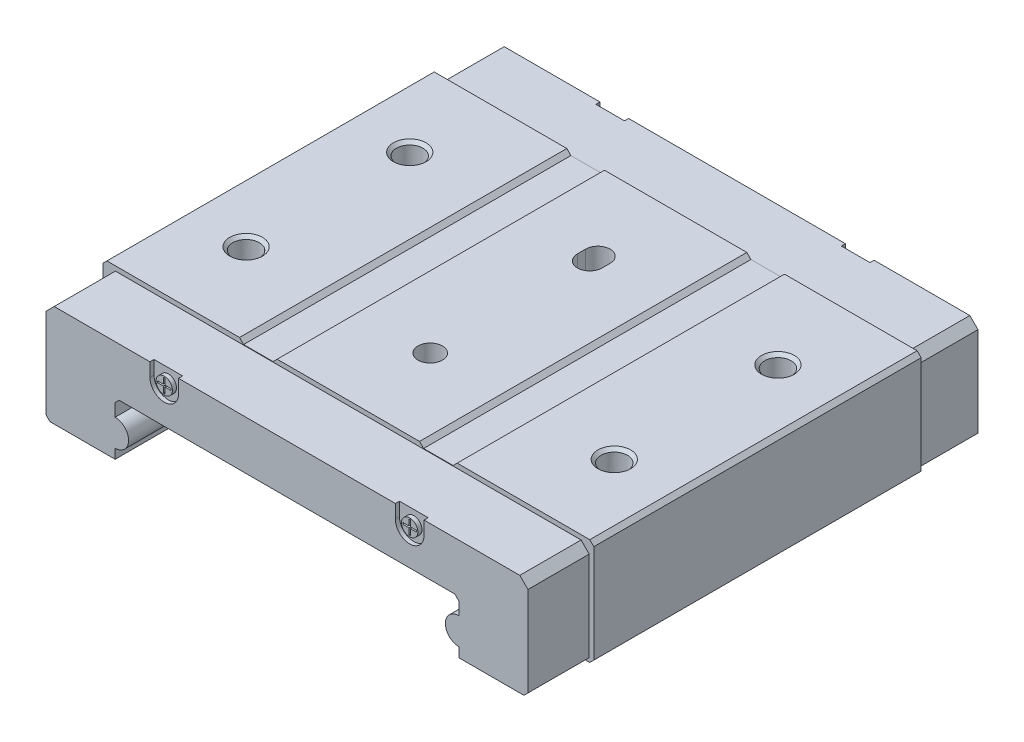
SolidWorks part; units mm, degrees
ref_plane "Front Plane" through (0, 0, 0) normal (0, 0, 1) x (1, 0, 0)
ref_plane "Top Plane" through (0, 0, 0) normal (0, 1, 0) x (1, 0, 0)
ref_plane "Right Plane" through (0, 0, 0) normal (1, 0, 0) x (0, 0, -1)
ref_plane "Plane1" through (0, 0, 0) normal (0, 0, 1) x (1, 0, 0)
sketch "Sketch1" plane through (0, 0, 0) normal (0, 0, 1) x (1, 0, 0)
  line L0 (-30, 12.505) -> (-30, 0.495)
  line L1 (-30, 0.495) -> (-29.505, 0)
  line L2 (-29.505, 0) -> (-21, 0)
  line L3 (-21, 0) -> (-21, 1.176)
  line L4 (-21, 4.456) -> (-21, 6.005)
  line L5 (-21, 6.005) -> (-20.505, 6.5)
  line L6 (-20.505, 6.5) -> (20.505, 6.5)
  line L7 (20.505, 6.5) -> (21, 6.005)
  line L8 (21, 6.005) -> (21, 4.456)
  line L9 (21, 1.176) -> (21, 0)
  line L10 (21, 0) -> (29.505, 0)
  line L11 (29.505, 0) -> (30, 0.495)
  line L12 (30, 0.495) -> (30, 12.505)
  line L13 (30, 12.505) -> (29.505, 13)
  line L14 (29.505, 13) -> (13.3, 13)
  line L15 (13.3, 13) -> (12.8, 12.5)
  line L16 (12.8, 12.5) -> (9.2, 12.5)
  line L17 (9.2, 12.5) -> (8.7, 13)
  line L18 (8.7, 13) -> (-8.7, 13)
  line L19 (-8.7, 13) -> (-9.2, 12.5)
  line L20 (-9.2, 12.5) -> (-12.8, 12.5)
  line L21 (-12.8, 12.5) -> (-13.3, 13)
  line L22 (-13.3, 13) -> (-29.505, 13)
  line L23 (-29.505, 13) -> (-30, 12.505)
  arc A0 (-21, 1.176) -> (-21, 4.456) centre (-21, 2.816) ccw
  arc A1 (21, 4.456) -> (21, 1.176) centre (21, 2.816) ccw
extrude "Boss-Extrude1" add sketch "Sketch1" against normal blind 20 and the other way blind 20
ref_plane "Plane2" through (0, 0, 20) normal (0, 0, 1) x (1, 0, 0)
sketch "Sketch2" plane through (0, 0, 20) normal (0, 0, 1) x (1, 0, 0)
  line L0 (-29.45, 11.453) -> (-29.45, 0.495)
  line L1 (-29.45, 0.495) -> (-28.955, 0)
  line L2 (-28.955, 0) -> (-21, 0)
  line L3 (-21, 0) -> (-21, 1.176)
  line L4 (-21, 4.456) -> (-21, 6.005)
  line L5 (-21, 6.005) -> (-20.505, 6.5)
  line L6 (-20.505, 6.5) -> (20.505, 6.5)
  line L7 (20.505, 6.5) -> (21, 6.005)
  line L8 (21, 6.005) -> (21, 4.456)
  line L9 (21, 1.176) -> (21, 0)
  line L10 (21, 0) -> (28.955, 0)
  line L11 (28.955, 0) -> (29.45, 0.495)
  line L12 (29.45, 0.495) -> (29.45, 11.453)
  line L13 (29.45, 11.453) -> (28.453, 12.45)
  line L14 (28.453, 12.45) -> (-28.453, 12.45)
  line L15 (-28.453, 12.45) -> (-29.45, 11.453)
  arc A0 (-21, 1.176) -> (-21, 4.456) centre (-21, 2.816) ccw
  arc A1 (21, 4.456) -> (21, 1.176) centre (21, 2.816) ccw
extrude "Boss-Extrude2" add sketch "Sketch2" against normal blind 7.5 and the other way blind 7.5
ref_plane "Plane3" through (0, 0, 20) normal (0, 0, 1) x (1, 0, 0)
sketch "Sketch3" plane through (0, 0, 20) normal (0, 0, 1) x (1, 0, 0)
  line L0 (-40, 40) -> (-40, -40)
  line L1 (-40, -40) -> (40, -40)
  line L2 (40, -40) -> (40, 40)
  line L3 (40, 40) -> (-40, 40)
  line L4 (-29.44, 11.443) -> (-29.44, 0.505)
  line L5 (-29.44, 0.505) -> (-28.945, 0.01)
  line L6 (-28.945, 0.01) -> (-21.01, 0.01)
  line L7 (-21.01, 0.01) -> (-21.01, 1.206)
  line L8 (-21.01, 4.446) -> (-21.01, 6.51)
  line L9 (-21.01, 6.51) -> (21.01, 6.51)
  line L10 (21.01, 6.51) -> (21.01, 4.446)
  line L11 (21.01, 1.206) -> (21.01, 0.01)
  line L12 (21.01, 0.01) -> (28.945, 0.01)
  line L13 (28.945, 0.01) -> (29.44, 0.505)
  line L14 (29.44, 0.505) -> (29.44, 11.443)
  line L15 (29.44, 11.443) -> (28.443, 12.44)
  line L16 (28.443, 12.44) -> (-28.443, 12.44)
  line L17 (-28.443, 12.44) -> (-29.44, 11.443)
  arc A0 (-21.01, 1.206) -> (-21.01, 4.446) centre (-21.01, 2.826) ccw
  arc A1 (21.01, 4.446) -> (21.01, 1.206) centre (21.01, 2.826) ccw
extrude "Cut-Extrude1" cut sketch "Sketch3" along normal blind 0.02
ref_plane "Plane4" through (0, 0, -20) normal (0, 0, 1) x (1, 0, 0)
sketch "Sketch4" plane through (0, 0, -20) normal (0, 0, 1) x (1, 0, 0)
  line L0 (-29.45, 11.453) -> (-29.45, 0.495)
  line L1 (-29.45, 0.495) -> (-28.955, 0)
  line L2 (-28.955, 0) -> (-21, 0)
  line L3 (-21, 0) -> (-21, 1.176)
  line L4 (-21, 4.456) -> (-21, 6.005)
  line L5 (-21, 6.005) -> (-20.505, 6.5)
  line L6 (-20.505, 6.5) -> (20.505, 6.5)
  line L7 (20.505, 6.5) -> (21, 6.005)
  line L8 (21, 6.005) -> (21, 4.456)
  line L9 (21, 1.176) -> (21, 0)
  line L10 (21, 0) -> (28.955, 0)
  line L11 (28.955, 0) -> (29.45, 0.495)
  line L12 (29.45, 0.495) -> (29.45, 11.453)
  line L13 (29.45, 11.453) -> (28.453, 12.45)
  line L14 (28.453, 12.45) -> (-28.453, 12.45)
  line L15 (-28.453, 12.45) -> (-29.45, 11.453)
  arc A0 (-21, 1.176) -> (-21, 4.456) centre (-21, 2.816) ccw
  arc A1 (21, 4.456) -> (21, 1.176) centre (21, 2.816) ccw
extrude "Boss-Extrude3" add sketch "Sketch4" against normal blind 7.5 and the other way blind 7.5
ref_plane "Plane5" through (0, 0, -20) normal (0, 0, 1) x (1, 0, 0)
sketch "Sketch5" plane through (0, 0, -20) normal (0, 0, 1) x (1, 0, 0)
  line L0 (-40, 40) -> (-40, -40)
  line L1 (-40, -40) -> (40, -40)
  line L2 (40, -40) -> (40, 40)
  line L3 (40, 40) -> (-40, 40)
  line L4 (-29.44, 11.443) -> (-29.44, 0.505)
  line L5 (-29.44, 0.505) -> (-28.945, 0.01)
  line L6 (-28.945, 0.01) -> (-21.01, 0.01)
  line L7 (-21.01, 0.01) -> (-21.01, 1.206)
  line L8 (-21.01, 4.446) -> (-21.01, 6.51)
  line L9 (-21.01, 6.51) -> (21.01, 6.51)
  line L10 (21.01, 6.51) -> (21.01, 4.446)
  line L11 (21.01, 1.206) -> (21.01, 0.01)
  line L12 (21.01, 0.01) -> (28.945, 0.01)
  line L13 (28.945, 0.01) -> (29.44, 0.505)
  line L14 (29.44, 0.505) -> (29.44, 11.443)
  line L15 (29.44, 11.443) -> (28.443, 12.44)
  line L16 (28.443, 12.44) -> (-28.443, 12.44)
  line L17 (-28.443, 12.44) -> (-29.44, 11.443)
  arc A0 (-21.01, 1.206) -> (-21.01, 4.446) centre (-21.01, 2.826) ccw
  arc A1 (21.01, 4.446) -> (21.01, 1.206) centre (21.01, 2.826) ccw
extrude "Cut-Extrude2" cut sketch "Sketch5" against normal blind 0.02
ref_plane "Plane6" through (0, 0, -27.5) normal (0, 0, 1) x (1, 0, 0)
sketch "Sketch6" plane through (0, 0, -27.5) normal (0, 0, 1) x (1, 0, 0)
  line L0 (-16.75, 32) -> (-16.75, 10.8)
  line L1 (-13.25, 10.8) -> (-13.25, 30.825)
  line L2 (-13.25, 30.825) -> (13.25, 30.825)
  line L3 (13.25, 30.825) -> (13.25, 10.8)
  line L4 (16.75, 10.8) -> (16.75, 32)
  line L5 (16.75, 32) -> (-16.75, 32)
  arc A0 (-16.75, 10.8) -> (-13.25, 10.8) centre (-15, 10.8) ccw
  arc A1 (13.25, 10.8) -> (16.75, 10.8) centre (15, 10.8) ccw
extrude "Cut-Extrude3" cut sketch "Sketch6" against normal blind 0.5 and the other way blind 0.5
ref_plane "Plane7" through (0, 0, 27.5) normal (0, 0, 1) x (1, 0, 0)
sketch "Sketch7" plane through (0, 0, 27.5) normal (0, 0, 1) x (1, 0, 0)
  line L0 (-16.75, 32) -> (-16.75, 10.8)
  line L1 (-13.25, 10.8) -> (-13.25, 30.825)
  line L2 (-13.25, 30.825) -> (13.25, 30.825)
  line L3 (13.25, 30.825) -> (13.25, 10.8)
  line L4 (16.75, 10.8) -> (16.75, 32)
  line L5 (16.75, 32) -> (-16.75, 32)
  arc A0 (-16.75, 10.8) -> (-13.25, 10.8) centre (-15, 10.8) ccw
  arc A1 (13.25, 10.8) -> (16.75, 10.8) centre (15, 10.8) ccw
extrude "Cut-Extrude4" cut sketch "Sketch7" against normal blind 0.5
ref_plane "Plane8" through (0, 0, -27.5) normal (0, 0, 1) x (1, 0, 0)
sketch "Sketch8" plane through (0, 0, -27.5) normal (0, 0, 1) x (1, 0, 0)
  line L0 (-15.85, 10.9) -> (-15.85, 10.7)
  line L1 (-15.85, 10.7) -> (-15.1, 10.7)
  line L2 (-15.1, 10.7) -> (-15.1, 9.95)
  line L3 (-15.1, 9.95) -> (-14.9, 9.95)
  line L4 (-14.9, 9.95) -> (-14.9, 10.7)
  line L5 (-14.9, 10.7) -> (-14.15, 10.7)
  line L6 (-14.15, 10.7) -> (-14.15, 10.9)
  line L7 (-14.15, 10.9) -> (-14.9, 10.9)
  line L8 (-14.9, 10.9) -> (-14.9, 11.65)
  line L9 (-14.9, 11.65) -> (-15.1, 11.65)
  line L10 (-15.1, 11.65) -> (-15.1, 10.9)
  line L11 (-15.1, 10.9) -> (-15.85, 10.9)
  circle A0 centre (-15, 10.8) radius 1
extrude "Boss-Extrude4" add sketch "Sketch8" along normal blind 0.5
ref_plane "Plane9" through (0, 0, -27.5) normal (0, 0, 1) x (1, 0, 0)
sketch "Sketch9" plane through (0, 0, -27.5) normal (0, 0, 1) x (1, 0, 0)
  line L0 (14.15, 10.9) -> (14.15, 10.7)
  line L1 (14.15, 10.7) -> (14.9, 10.7)
  line L2 (14.9, 10.7) -> (14.9, 9.95)
  line L3 (14.9, 9.95) -> (15.1, 9.95)
  line L4 (15.1, 9.95) -> (15.1, 10.7)
  line L5 (15.1, 10.7) -> (15.85, 10.7)
  line L6 (15.85, 10.7) -> (15.85, 10.9)
  line L7 (15.85, 10.9) -> (15.1, 10.9)
  line L8 (15.1, 10.9) -> (15.1, 11.65)
  line L9 (15.1, 11.65) -> (14.9, 11.65)
  line L10 (14.9, 11.65) -> (14.9, 10.9)
  line L11 (14.9, 10.9) -> (14.15, 10.9)
  circle A0 centre (15, 10.8) radius 1
extrude "Boss-Extrude5" add sketch "Sketch9" along normal blind 0.5
ref_plane "Plane10" through (0, 0, 27.5) normal (0, 0, 1) x (1, 0, 0)
sketch "Sketch10" plane through (0, 0, 27.5) normal (0, 0, 1) x (1, 0, 0)
  line L0 (-15.85, 10.9) -> (-15.85, 10.7)
  line L1 (-15.85, 10.7) -> (-15.1, 10.7)
  line L2 (-15.1, 10.7) -> (-15.1, 9.95)
  line L3 (-15.1, 9.95) -> (-14.9, 9.95)
  line L4 (-14.9, 9.95) -> (-14.9, 10.7)
  line L5 (-14.9, 10.7) -> (-14.15, 10.7)
  line L6 (-14.15, 10.7) -> (-14.15, 10.9)
  line L7 (-14.15, 10.9) -> (-14.9, 10.9)
  line L8 (-14.9, 10.9) -> (-14.9, 11.65)
  line L9 (-14.9, 11.65) -> (-15.1, 11.65)
  line L10 (-15.1, 11.65) -> (-15.1, 10.9)
  line L11 (-15.1, 10.9) -> (-15.85, 10.9)
  circle A0 centre (-15, 10.8) radius 1
extrude "Boss-Extrude6" add sketch "Sketch10" against normal blind 0.5
ref_plane "Plane11" through (0, 0, 27.5) normal (0, 0, 1) x (1, 0, 0)
sketch "Sketch11" plane through (0, 0, 27.5) normal (0, 0, 1) x (1, 0, 0)
  line L0 (14.15, 10.9) -> (14.15, 10.7)
  line L1 (14.15, 10.7) -> (14.9, 10.7)
  line L2 (14.9, 10.7) -> (14.9, 9.95)
  line L3 (14.9, 9.95) -> (15.1, 9.95)
  line L4 (15.1, 9.95) -> (15.1, 10.7)
  line L5 (15.1, 10.7) -> (15.85, 10.7)
  line L6 (15.85, 10.7) -> (15.85, 10.9)
  line L7 (15.85, 10.9) -> (15.1, 10.9)
  line L8 (15.1, 10.9) -> (15.1, 11.65)
  line L9 (15.1, 11.65) -> (14.9, 11.65)
  line L10 (14.9, 11.65) -> (14.9, 10.9)
  line L11 (14.9, 10.9) -> (14.15, 10.9)
  circle A0 centre (15, 10.8) radius 1
extrude "Boss-Extrude7" add sketch "Sketch11" against normal blind 0.5
ref_plane "Plane12" through (22.5, 0, 0) normal (1, 0, 0) x (0, 0, -1)
sketch "Sketch12" plane through (22.5, 0, 0) normal (1, 0, 0) x (0, 0, -1)
  line L0 (-10, 13) -> (-8, 13)
  line L1 (-8, 13) -> (-8.379, 12.621)
  line L2 (-8.379, 12.621) -> (-8.379, 7.1859)
  line L3 (-8.379, 7.1859) -> (-10, 6.25)
  line L4 (-10, 6.25) -> (-10, 13)
  line L5 (-10, 6.25) -> (-10, 13) construction
revolve "Cut-Revolve1" cut sketch "Sketch12" angle 360 about L5 reverse direction yes
ref_plane "Plane13" through (-22.5, 0, 0) normal (1, 0, 0) x (0, 0, -1)
sketch "Sketch13" plane through (-22.5, 0, 0) normal (1, 0, 0) x (0, 0, -1)
  line L0 (10, 13) -> (12, 13)
  line L1 (12, 13) -> (11.621, 12.621)
  line L2 (11.621, 12.621) -> (11.621, 7.1859)
  line L3 (11.621, 7.1859) -> (10, 6.25)
  line L4 (10, 6.25) -> (10, 13)
  line L5 (10, 6.25) -> (10, 13) construction
revolve "Cut-Revolve2" cut sketch "Sketch13" angle 360 about L5 reverse direction yes
ref_plane "Plane14" through (22.5, 0, 0) normal (1, 0, 0) x (0, 0, -1)
sketch "Sketch14" plane through (22.5, 0, 0) normal (1, 0, 0) x (0, 0, -1)
  line L0 (10, 13) -> (12, 13)
  line L1 (12, 13) -> (11.621, 12.621)
  line L2 (11.621, 12.621) -> (11.621, 7.1859)
  line L3 (11.621, 7.1859) -> (10, 6.25)
  line L4 (10, 6.25) -> (10, 13)
  line L5 (10, 6.25) -> (10, 13) construction
revolve "Cut-Revolve3" cut sketch "Sketch14" angle 360 about L5 reverse direction yes
ref_plane "Plane15" through (-22.5, 0, 0) normal (1, 0, 0) x (0, 0, -1)
sketch "Sketch15" plane through (-22.5, 0, 0) normal (1, 0, 0) x (0, 0, -1)
  line L0 (-10, 13) -> (-8, 13)
  line L1 (-8, 13) -> (-8.379, 12.621)
  line L2 (-8.379, 12.621) -> (-8.379, 7.1859)
  line L3 (-8.379, 7.1859) -> (-10, 6.25)
  line L4 (-10, 6.25) -> (-10, 13)
  line L5 (-10, 6.25) -> (-10, 13) construction
revolve "Cut-Revolve4" cut sketch "Sketch15" angle 360 about L5 reverse direction yes
ref_plane "Plane16" through (0, 0, 10) normal (0, 0, 1) x (1, 0, 0)
sketch "Sketch16" plane through (0, 0, 10) normal (0, 0, 1) x (1, 0, 0)
  line L0 (0, 13) -> (1.5, 13)
  line L1 (1.5, 13) -> (1.5, 9)
  line L2 (1.5, 9) -> (0, 9)
  line L3 (0, 9) -> (0, 13)
  line L4 (0, 9) -> (0, 13) construction
revolve "Cut-Revolve5" cut sketch "Sketch16" angle 360 about L4 reverse direction yes
ref_plane "Plane17" through (0, 13, 0) normal (0, 1, 0) x (-1, 0, 0)
sketch "Sketch17" plane through (0, 13, 0) normal (0, 1, 0) x (-1, 0, 0)
  line L0 (1.5, -10.5) -> (1.5, -9.5)
  line L1 (-1.5, -9.5) -> (-1.5, -10.5)
  arc A0 (1.5, -9.5) -> (-1.5, -9.5) centre (0, -9.5) ccw
  arc A1 (-1.5, -10.5) -> (1.5, -10.5) centre (0, -10.5) ccw
extrude "Cut-Extrude5" cut sketch "Sketch17" against normal blind 4
